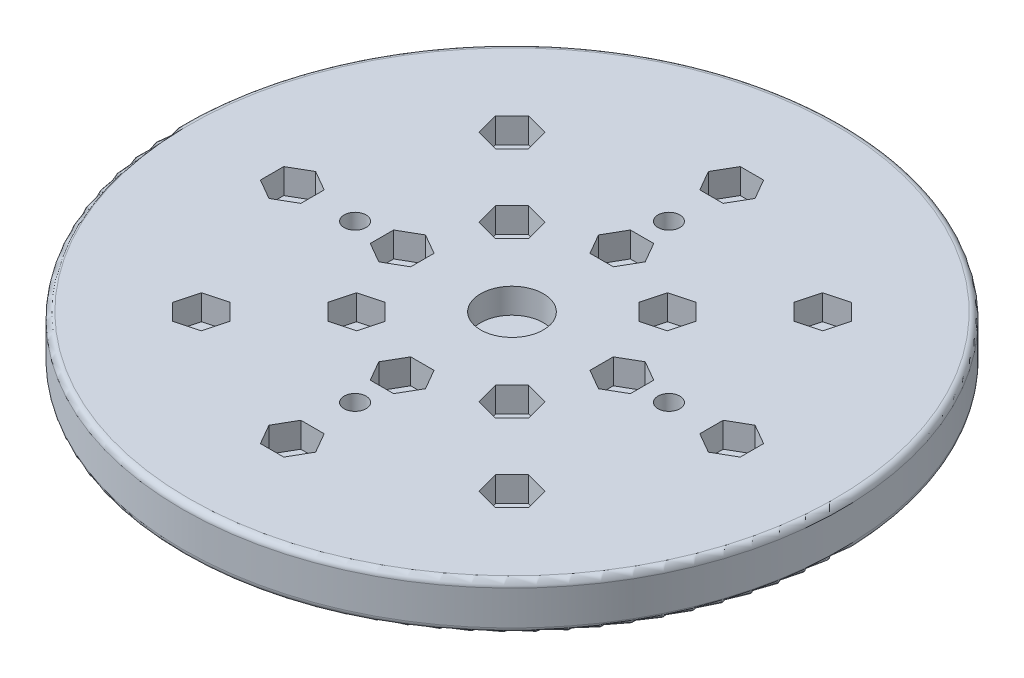
SolidWorks part; units mm, degrees
ref_plane "Front Plane" through (0, 0, 0) normal (0, 0, 1) x (1, 0, 0)
ref_plane "Top Plane" through (0, 0, 0) normal (0, 1, 0) x (1, 0, 0)
ref_plane "Right Plane" through (0, 0, 0) normal (1, 0, 0) x (0, 0, -1)
sketch "Sketch1" plane through (0, 0, 0) normal (0, 1, 0) x (1, 0, 0)
  circle A0 centre (0, 0) radius 105
  dimension "D1" = 210
extrude "Boss-Extrude1" add sketch "Sketch1" along normal mid plane 15
sketch "Sketch2" plane through (0, 0, 0) normal (0, 1, 0) x (1, 0, 0)
  line L0 (-105, 0) -> (105, 0) construction
  line L1 (0, 50) -> (0, -50) construction
  circle A0 centre (0, 0) radius 105 construction
  circle A1 centre (0, 50) radius 3.5
  circle A2 centre (0, -50) radius 3.5
  dimension "D1" = 100
  dimension "D2" = 7
extrude "Cut-Extrude2" cut sketch "Sketch2" against normal mid plane 15
pattern_circular "CirPattern1" count 2 every 90 about axis through (0, 7.5, 0) along (0, 1, 0) of "Cut-Extrude2"
fillet "Fillet2" radius 2 2 edges at (0, -7.5, 105) (0, 7.5, 105)
sketch "Sketch3" plane through (0, 7.5, 0) normal (0, 1, 0) x (1, 0, 0)
  line L12 (3.7183, 6.4402) -> (-3.7183, 6.4402)
  line L13 (-3.7183, 6.4402) -> (-7.4365, 0)
  line L14 (-7.4365, 0) -> (-3.7183, -6.4402)
  line L15 (-3.7183, -6.4402) -> (3.7183, -6.4402)
  line L16 (3.7183, -6.4402) -> (7.4365, 0)
  line L17 (7.4365, 0) -> (3.7183, 6.4402)
  line L18 (-3.7183, 6.4402) -> (3.7183, -6.4402) construction
  dimension "D1" = 120
  dimension "D2" = 120
  dimension "D3" = 120
  dimension "D4" = 7.4365
  dimension "D5" = 120
  dimension "D6" = 120
  dimension "D7" = 120
extrude "Cut-Extrude3" cut sketch "Sketch3" against normal blind 8
pattern_linear "LPattern1" count 3 spacing 35 along (0, 0, 1) of "Cut-Extrude3"
pattern_circular "CirPattern2" count 8 over 360 about axis through (0, 7.5, 0) along (0, 1, 0) of "LPattern1"
sketch "Sketch4" plane through (0, 7.5, 0) normal (0, 1, 0) x (1, 0, 0)
  circle A0 centre (0, 0) radius 10
  dimension "D1" = 20
extrude "Cut-Extrude4" cut sketch "Sketch4" against normal up to surface (8 mm away) up to face at (0, -0.5, 0)
